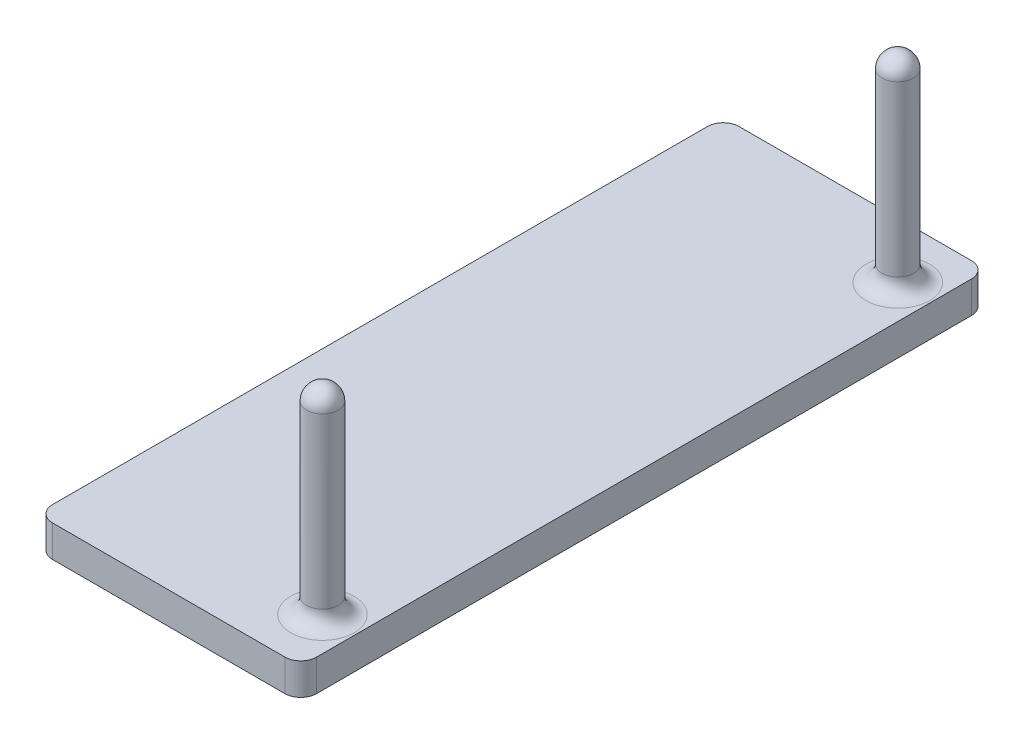
SolidWorks part; units mm, degrees
ref_plane "Front Plane" through (0, 0, 0) normal (0, 0, 1) x (1, 0, 0)
ref_plane "Top Plane" through (0, 0, 0) normal (0, 1, 0) x (1, 0, 0)
ref_plane "Right Plane" through (0, 0, 0) normal (1, 0, 0) x (0, 0, -1)
sketch "Sketch1" plane through (0, 0, 0) normal (0, 1, 0) x (1, 0, 0)
  line L1 (-12.5, -32.5) -> (12.5, -32.5)
  line L2 (-12.5, -32.5) -> (-12.5, 32.5)
  line L3 (-12.5, 32.5) -> (12.5, 32.5)
  line L4 (12.5, -32.5) -> (12.5, 32.5)
  line L5 (-12.5, -32.5) -> (12.5, 32.5) construction
  line L6 (-12.5, 32.5) -> (12.5, -32.5) construction
  point P0 (0, 0)
  dimension "D1" = 65
  dimension "D2" = 25
extrude "Boss-Extrude1" add sketch "Sketch1" along normal blind 3
sketch "Sketch2" plane through (0, 3, 0) normal (0, 1, 0) x (1, 0, 0)
  line L0 (-70.6517, 0) -> (70.6517, 0) construction
  line L1 (12.5, -32.5) -> (12.5, 32.5) construction
  circle A0 centre (9.2897, 27.2349) radius 1.5
  circle A1 centre (9.2897, -27.2349) radius 1.5
  point P8 (0, 0)
  dimension "D1" = 3
  dimension "D2" = 3.2103
  dimension "D3" = 54.4698
extrude "Boss-Extrude2" add sketch "Sketch2" along normal blind 19
fillet "Fillet1" radius 1.5 8 edges at (9.2897, 3, -28.7349) (9.2897, 3, 25.7349) (12.5, 1.5, 32.5) (-12.5, 1.5, -32.5) (12.5, 1.5, -32.5) (-12.5, 1.5, 32.5) (9.2897, 22, 28.7349) (9.2897, 22, -25.7349)
